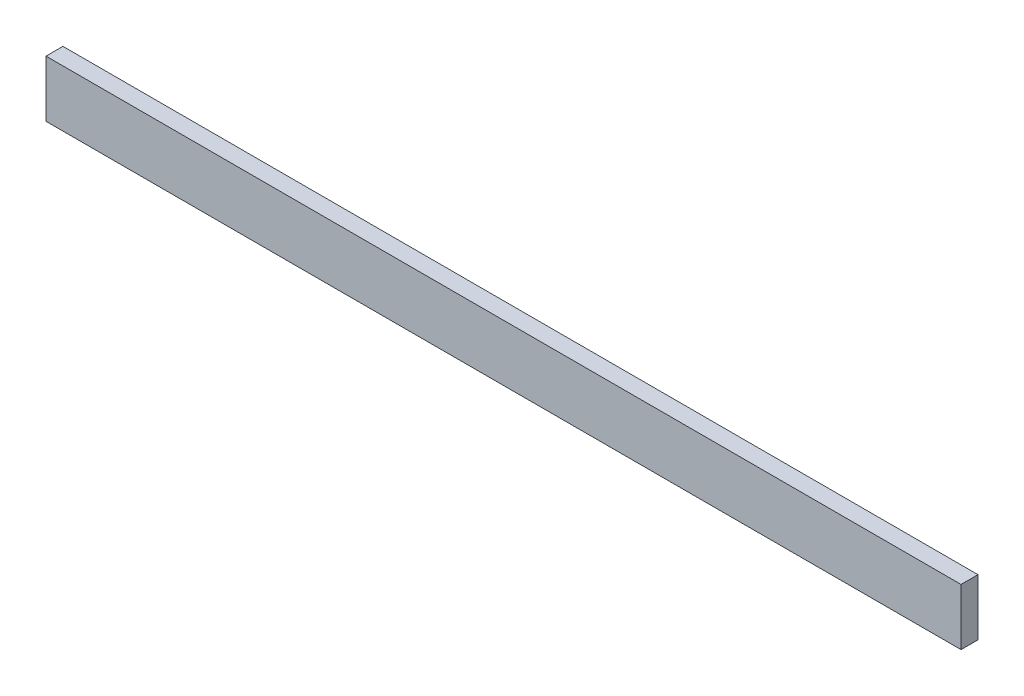
SolidWorks part; units mm, degrees
material "Cedar"
ref_plane "Front Plane" through (0, 0, 0) normal (0, 0, 1) x (1, 0, 0)
ref_plane "Top Plane" through (0, 0, 0) normal (0, 1, 0) x (1, 0, 0)
ref_plane "Right Plane" through (0, 0, 0) normal (1, 0, 0) x (0, 0, -1)
sketch "Sketch1" plane through (0, 0, 0) normal (1, 0, 0) x (0, 0, -1)
  line L1 (-9.525, -31.75) -> (9.525, -31.75)
  line L2 (-9.525, -31.75) -> (-9.525, 31.75)
  line L3 (-9.525, 31.75) -> (9.525, 31.75)
  line L4 (9.525, -31.75) -> (9.525, 31.75)
  line L5 (-9.525, -31.75) -> (9.525, 31.75) construction
  line L6 (-9.525, 31.75) -> (9.525, -31.75) construction
  point P0 (0, 0)
  dimension "D1" = 63.5
  dimension "D2" = 19.05
extrude "Boss-Extrude1" add sketch "Sketch1" along normal blind 514.35 and the other way blind 514.35
